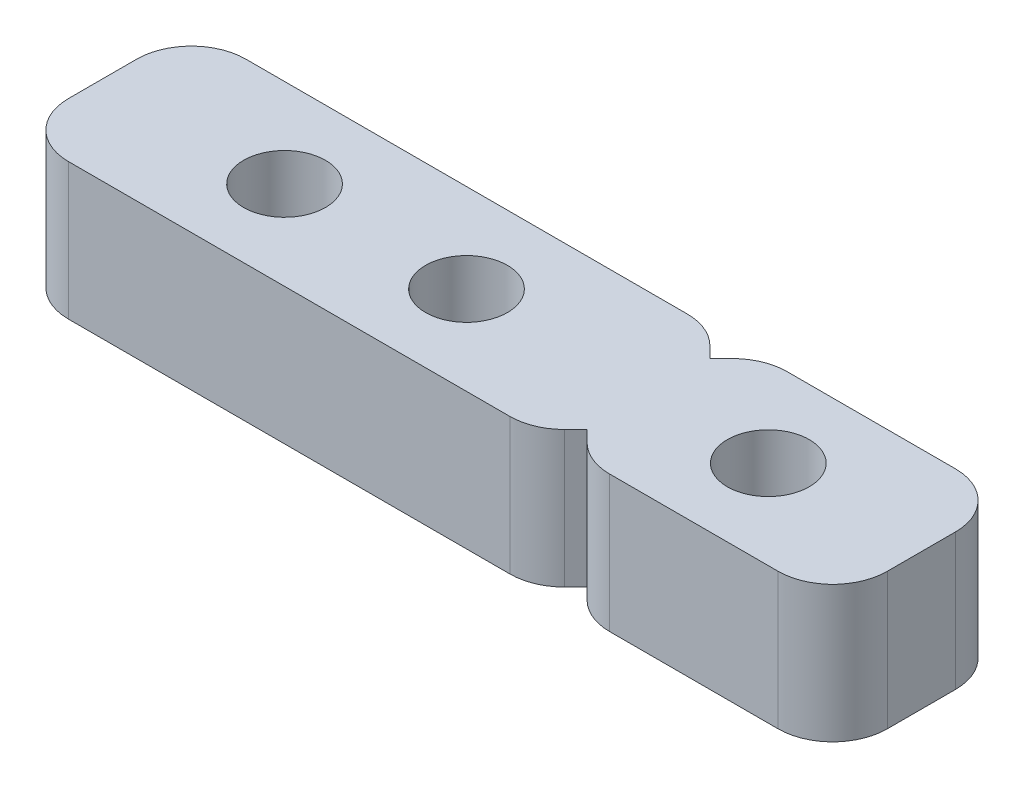
SolidWorks part; units mm, degrees
ref_plane "Front Plane" through (0, 0, 0) normal (0, 0, 1) x (1, 0, 0)
ref_plane "Top Plane" through (0, 0, 0) normal (0, 1, 0) x (1, 0, 0)
ref_plane "Right Plane" through (0, 0, 0) normal (1, 0, 0) x (0, 0, -1)
sketch "Sketch1" plane through (0, 0, 0) normal (0, 1, 0) x (1, 0, 0)
  line L0 (-21.0761, -4.5212) -> (-19.8061, -5.7912)
  line L1 (-45.2061, -4.5212) -> (-21.0761, -4.5212)
  line L2 (-45.2061, -4.5212) -> (-45.2061, -12.7762)
  line L3 (-45.2061, -12.7762) -> (-21.0761, -12.7762)
  line L4 (-7.1061, -4.5212) -> (-7.1061, -12.7762)
  line L5 (-19.8061, -5.7912) -> (-18.5361, -4.5212)
  line L6 (-18.5361, -4.5212) -> (-7.1061, -4.5212)
  line L8 (-21.0761, -12.7762) -> (-19.8061, -11.5062)
  line L9 (-19.8061, -11.5062) -> (-18.5361, -12.7762)
  line L10 (-18.5361, -12.7762) -> (-7.1061, -12.7762)
  circle A2 centre (-36.7395, -8.6487) radius 1.905
  circle A3 centre (-28.2728, -8.6487) radius 1.905
  circle A5 centre (-14.2308, -8.6487) radius 1.905
extrude "Boss-Extrude1" add sketch "Sketch1" along normal blind 6.35
fillet "Fillet1" radius 2.54 8 edges at (-45.2061, 3.175, 4.5212) (-21.0761, 3.175, 4.5212) (-18.5361, 3.175, 4.5212) (-7.1061, 3.175, 4.5212) (-7.1061, 3.175, 12.7762) (-18.5361, 3.175, 12.7762) (-21.0761, 3.175, 12.7762) (-45.2061, 3.175, 12.7762)
